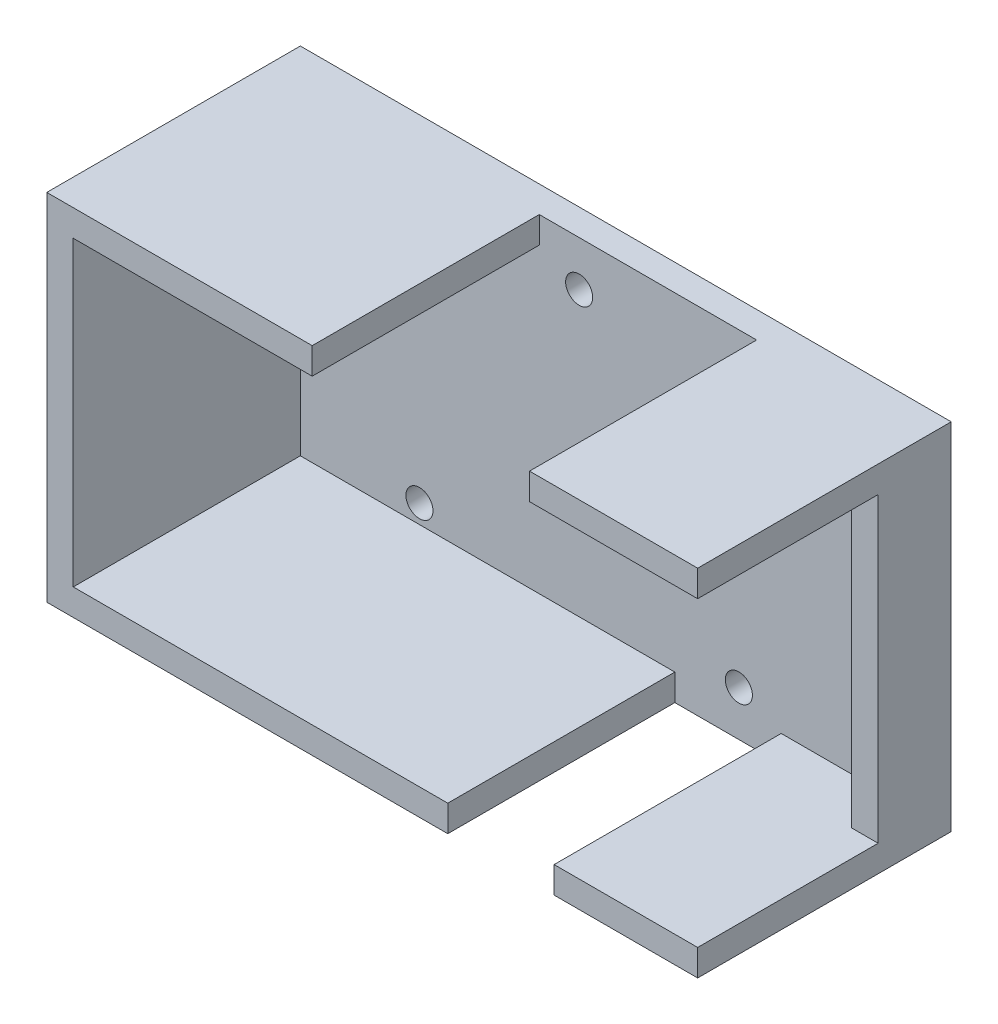
SolidWorks part; units mm, degrees
ref_plane "Front Plane" through (0, 0, 0) normal (0, 0, 1) x (1, 0, 0)
ref_plane "Top Plane" through (0, 0, 0) normal (0, 1, 0) x (1, 0, 0)
ref_plane "Right Plane" through (0, 0, 0) normal (1, 0, 0) x (0, 0, -1)
sketch "Sketch1" plane through (0, 0, 0) normal (0, 0, 1) x (1, 0, 0)
  line L1 (-27.4828, -14.986) -> (27.4828, -14.986)
  line L2 (-27.4828, -14.986) -> (-27.4828, 14.986)
  line L3 (-27.4828, 14.986) -> (27.4828, 14.986)
  line L4 (27.4828, -14.986) -> (27.4828, 14.986)
  line L5 (-27.4828, -14.986) -> (27.4828, 14.986) construction
  line L6 (-27.4828, 14.986) -> (27.4828, -14.986) construction
  point P0 (0, 0)
  dimension "D1" = 54.9656
  dimension "D2" = 29.972
extrude "Boss-Extrude1" add sketch "Sketch1" along normal blind 21.4122
shell "Shell1" thickness 2.2352 removed face at (0, 0, 21.4122)
sketch "Sketch2" plane through (0, 0, 0) normal (0, 0, -1) x (-1, 0, 0)
  line L0 (27.4828, 11.176) -> (1.7018, 11.176) construction
  line L2 (27.4828, 14.986) -> (27.4828, -14.986) construction
  line L3 (27.4828, -11.176) -> (15.1892, -11.176) construction
  line L4 (15.1892, -11.176) -> (-11.7856, -11.176) construction
  line L5 (-27.4828, 14.986) -> (27.4828, 14.986) construction
  circle A0 centre (1.7018, 11.176) radius 1.143
  circle A1 centre (-11.7856, -11.176) radius 1.143
  circle A2 centre (15.1892, -11.176) radius 1.143
  dimension "D6" = 2.286
  dimension "D1" = 26.9748
  dimension "D2" = 13.4874
  dimension "D3" = 22.352
  dimension "D4" = 12.2936
  dimension "D5" = 3.81
extrude "Cut-Extrude1" cut sketch "Sketch2" against normal through all
sketch "Sketch3" plane through (0, 0, 21.4122) normal (0, 0, 1) x (1, 0, 0)
  line L0 (27.4828, -14.986) -> (27.4828, 14.986) construction
  line L1 (25.2476, -12.7508) -> (27.4828, -12.7508)
  line L2 (25.2476, -12.7508) -> (25.2476, 12.7508)
  line L3 (25.2476, 12.7508) -> (27.4828, 12.7508)
  line L4 (27.4828, -12.7508) -> (27.4828, 12.7508)
extrude "Cut-Extrude2" cut sketch "Sketch3" against normal blind 15.24
sketch "Sketch4" plane through (0, 0, 21.4122) normal (0, 0, 1) x (1, 0, 0)
  line L0 (-27.4828, -14.986) -> (27.4828, -14.986) construction
  line L1 (15.361, -14.986) -> (6.3795, -14.986)
  line L2 (15.361, -14.986) -> (15.361, -12.7508)
  line L3 (15.361, -12.7508) -> (6.3795, -12.7508)
  line L4 (6.3795, -14.986) -> (6.3795, -12.7508)
  line L5 (-25.2476, -12.7508) -> (27.4828, -12.7508) construction
  line L6 (27.4828, 14.986) -> (-27.4828, 14.986) construction
  line L7 (-5.0683, 14.986) -> (13.284, 14.986)
  line L8 (-5.0683, 14.986) -> (-5.0683, 12.7508)
  line L9 (-5.0683, 12.7508) -> (13.284, 12.7508)
  line L10 (13.284, 14.986) -> (13.284, 12.7508)
  line L11 (27.4828, 12.7508) -> (-25.2476, 12.7508) construction
extrude "Cut-Extrude3" cut sketch "Sketch4" against normal up to surface (19.177 mm away) up to face at (-16.3322, -11.176, 2.2352)
sketch "Sketch6" plane through (-27.4828, 0, 0) normal (-1, 0, 0) x (0, 0, 1)
  line L0 (0, 14.986) -> (0, -14.986) construction
  line L1 (0, 7.366) -> (0.635, 7.366)
  line L2 (0, 7.366) -> (0, 5.5372)
  line L3 (0, 5.5372) -> (0.635, 5.5372)
  line L4 (0.635, 7.366) -> (0.635, 5.5372)
  line L5 (21.4122, 14.986) -> (0, 14.986) construction
  line L6 (0, -5.3848) -> (0.635, -5.3848)
  line L7 (0, -5.3848) -> (0, -7.2136)
  line L8 (0, -7.2136) -> (0.635, -7.2136)
  line L9 (0.635, -5.3848) -> (0.635, -7.2136)
  dimension "D1" = 1.8288
  dimension "D2" = 0.635
  dimension "D3" = 10.922
  dimension "D4" = 7.62
extrude "Boss-Extrude2" add sketch "Sketch6" along normal blind 5.08
